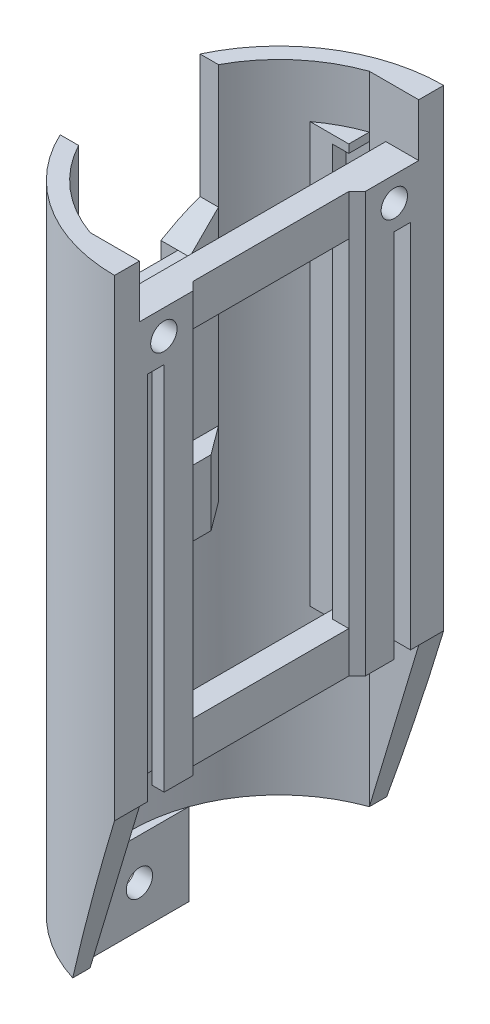
SolidWorks part; units mm, degrees
ref_plane "前视基准面" through (0, 0, 0) normal (0, 0, 1) x (1, 0, 0)
ref_plane "上视基准面" through (0, 0, 0) normal (0, 1, 0) x (1, 0, 0)
ref_plane "右视基准面" through (0, 0, 0) normal (1, 0, 0) x (0, 0, -1)
other "Configuration Table"
sketch "草图1" plane through (0, 0, 0) normal (0, 1, 0) x (1, 0, 0)
  line L0 (0, -473.638) -> (0, 23208.2609) construction
  line L1 (0, 0) -> (-4, 0) construction
  line L2 (0, 20) -> (0, -20)
  line L3 (-4, -17.5499) -> (-4, 17.5499)
  arc A0 (0, 20) -> (0, -20) centre (0, 0) ccw
  arc A1 (-4, 17.5499) -> (-4, -17.5499) centre (0, 0) ccw
  point P12 (-4, 0)
  dimension "D1" = 40
  dimension "D2" = 36
  dimension "D3" = 4
extrude "凸台-拉伸1" add sketch "草图1" along normal blind 70
sketch "草图3" plane through (0, 0, 0) normal (1, 0, 0) x (0, 0, -1)
  line L0 (-20, 0) -> (20, 0) construction
  line L1 (-16, 60) -> (16, 60) construction
  line L2 (-16, 60) -> (-16, 0) construction
  line L3 (-16, 0) -> (16, 0) construction
  line L4 (16, 60) -> (16, 0) construction
  line L5 (-20, 70) -> (20, 70) construction
  circle A0 centre (-14, 58) radius 2 construction
  circle A1 centre (14, 58) radius 2 construction
  circle A2 centre (-14, 58) radius 1
  circle A3 centre (14, 58) radius 1
  point P4 (0, 60)
  dimension "D4" = 4
  dimension "D5" = 4
  dimension "D6" = 2
  dimension "D7" = 2
  dimension "D1" = 0
  dimension "D2" = 10
  dimension "D3" = 32
extrude "切除-拉伸2" cut sketch "草图3" against normal up to surface (4 mm away) from surface up to face at (-4, 35, 0) starting at face at (0, 35, 0)
sketch "草图5" plane through (0, 0, 0) normal (0, 1, 0) x (1, 0, 0)
  line L0 (0, -1000) -> (0, 49000) construction
  line L1 (-1000, 0) -> (49000, 0) construction
  line L2 (-6, 16.9706) -> (6, 16.9706) construction
  line L3 (-6, -16.9706) -> (6, -16.9706) construction
  line L4 (0, 16.9706) -> (0, -16.9706)
  line L5 (0, -16.9706) -> (-4, -16.9706)
  line L6 (-4, -17.5499) -> (-4, 17.5499) construction
  line L7 (-4, -16.9706) -> (-4, 16.9706)
  line L8 (-4, 16.9706) -> (0, 16.9706)
  circle A0 centre (0, 0) radius 18 construction
  point P11 (0, 16.9706)
  dimension "D1" = 12
extrude "切除-拉伸4" cut sketch "草图5" against normal blind 9 from surface starting at face at (-10, 70, 0)
sketch "草图6" plane through (0, 0, 0) normal (0, 1, 0) x (1, 0, 0)
  line L0 (-4, 16.9706) -> (-6, 16.9706)
  line L1 (0, 16.9706) -> (0, 18)
  line L2 (-4, -16.9706) -> (-6, -16.9706)
  line L3 (0, -16.9706) -> (0, -18)
  line L4 (-4, 16.9706) -> (-4, -16.9706)
  line L5 (0, 16.9706) -> (-4, 16.9706)
  line L6 (0, -16.9706) -> (0, 16.9706)
  line L7 (-4, -16.9706) -> (0, -16.9706)
  line L9 (0, 16.9706) -> (-4, 16.9706)
  line L11 (-4, -16.9706) -> (0, -16.9706)
  arc A0 (0, 18) -> (-6, 16.9706) centre (0, 0) ccw
  arc A1 (-6, -16.9706) -> (0, -18) centre (0, 0) ccw
  dimension "D1" = 0
extrude "凸台-拉伸2" add sketch "草图6" against normal up to surface from surface up to face at (-10, 0, 0) starting at face at (-6.25, 70, 0)
sketch "草图7" plane through (0, 0, 0) normal (0, 1, 0) x (1, 0, 0)
  line L4 (-4, 16.9706) -> (-4, -16.9706)
  line L5 (0, 16.9706) -> (-4, 16.9706)
  line L6 (0, -16.9706) -> (0, 16.9706)
  line L7 (-4, -16.9706) -> (0, -16.9706)
  line L8 (-4, 16.9706) -> (-4, -16.9706)
  line L9 (0, 16.9706) -> (-4, 16.9706)
  line L10 (0, -16.9706) -> (0, 16.9706)
  line L11 (-4, -16.9706) -> (0, -16.9706)
  dimension "D1" = 0
extrude "切除-拉伸5" cut sketch "草图7" along normal blind 10
sketch "草图8" plane through (0, 0, 0) normal (0, 1, 0) x (1, 0, 0)
  line L0 (0, 16.9706) -> (0, -16.9706) construction
  line L1 (-6, 16.9706) -> (0, 16.9706)
  line L2 (-6, 16.9706) -> (-6, 14.4706)
  line L3 (-6, 14.4706) -> (0, 14.4706)
  line L4 (0, 16.9706) -> (0, 14.4706)
  line L6 (0, -16.9706) -> (-6, -16.9706)
  line L7 (0, -16.9706) -> (0, -14.4706)
  line L8 (0, -14.4706) -> (-6, -14.4706)
  line L9 (-6, -16.9706) -> (-6, -14.4706)
  dimension "D1" = 2.5
  dimension "D2" = 2.5
extrude "凸台-拉伸3" add sketch "草图8" against normal blind 1 from surface starting at face at (-2, 61, 0)
sketch "草图10" plane through (0, 0, 0) normal (0, 1, 0) x (1, 0, 0)
  line L0 (-6, 16.9706) -> (-6, 14.4706)
  line L1 (-6, 14.4706) -> (-10.7053, 14.4706)
  line L2 (-6, -14.4706) -> (-10.7053, -14.4706)
  line L3 (-6, -14.4706) -> (-6, -16.9706)
  arc A0 (-6, 16.9706) -> (-10.7053, 14.4706) centre (0, 0) ccw
  arc A1 (-10.7053, -14.4706) -> (-6, -16.9706) centre (0, 0) ccw
extrude "凸台-拉伸4" add sketch "草图10" along normal up to surface (70 mm away) from surface up to face at (-7.3333, 70, 0) starting at face at (-7.3333, 0, 0)
sketch "草图11" plane through (0, 0, 0) normal (0, 1, 0) x (1, 0, 0)
  line L0 (0, 16.9706) -> (0, -16.9706) construction
  line L1 (-6, 16.9706) -> (0, 16.9706)
  line L2 (-6, 16.9706) -> (-6, 14.4706)
  line L3 (-6, 14.4706) -> (0, 14.4706)
  line L4 (0, 16.9706) -> (0, 14.4706)
  line L5 (-6, 14.4706) -> (-10.7053, 14.4706) construction
  line L7 (-6, -14.4706) -> (0, -14.4706)
  line L8 (-6, -14.4706) -> (-6, -16.9706)
  line L9 (-6, -16.9706) -> (0, -16.9706)
  line L10 (0, -14.4706) -> (0, -16.9706)
  dimension "D1" = 0
extrude "凸台-拉伸5" add sketch "草图11" along normal up to surface (70 mm away) from surface up to face at (-7.2705, 70, 0) starting at face at (-4, 61, 0)
sketch "草图12" plane through (0, 0, 0) normal (0, 0, 1) x (1, 0, 0)
  line L1 (-6, 60) -> (-4, 60)
  line L2 (-6, 60) -> (-6, 61)
  line L3 (-6, 61) -> (-4, 61)
  line L4 (-4, 60) -> (-4, 61)
extrude "切除-拉伸6" cut sketch "草图12" against normal up to surface (16.9706 mm away) from surface up to face at (-3.3333, 23.3333, -16.9706) starting at face at (-3.3333, 23.3333, 16.9706)
sketch "草图14" plane through (0, 0, 0) normal (0, 1, 0) x (1, 0, 0)
  line L0 (-4, -14.4706) -> (-4, 14.4706) construction
  line L1 (-4, 10.4706) -> (-3, 10.4706)
  line L2 (-4, 10.4706) -> (-4, -10.4706)
  line L3 (-4, -10.4706) -> (-3, -10.4706)
  line L4 (-3, 10.4706) -> (-3, -10.4706)
  line L5 (-10.7053, -14.4706) -> (0, -14.4706) construction
  line L6 (-4, 14.4706) -> (0, 14.4706) construction
  line L7 (0, 14.4706) -> (0, -14.4706) construction
  line L8 (-1, 10.4706) -> (0, 10.4706)
  line L9 (-1, 10.4706) -> (-1, -10.4706)
  line L10 (-1, -10.4706) -> (0, -10.4706)
  line L11 (0, 10.4706) -> (0, -10.4706)
  line L12 (0, -14.4706) -> (-4, -14.4706) construction
  line L13 (0, 14.4706) -> (-10.7053, 14.4706) construction
  dimension "D1" = 1
  dimension "D2" = 4
  dimension "D3" = 4
  dimension "D4" = 1
  dimension "D5" = 4
  dimension "D6" = 4
extrude "切除-拉伸8" cut sketch "草图14" along normal up to surface (61 mm away) from surface up to face at (-2, 61, 0) starting at face at (-2, 10, 0)
sketch "草图15" plane through (0, 0, 0) normal (1, 0, 0) x (0, 0, -1)
  line L0 (10.4706, 61) -> (10.4706, 10) construction
  line L5 (-10.4706, 61) -> (-10.4706, 10) construction
  line L6 (10.4706, 61) -> (-10.4706, 61) construction
  line L7 (-10.4706, 10) -> (10.4706, 10) construction
  line L9 (-9.4706, 56) -> (9.4706, 56)
  line L10 (-9.4706, 56) -> (-9.4706, 15)
  line L11 (-9.4706, 15) -> (9.4706, 15)
  line L12 (9.4706, 56) -> (9.4706, 15)
  dimension "D1" = 1
  dimension "D2" = 1
  dimension "D3" = 5
  dimension "D4" = 5
extrude "切除-拉伸9" cut sketch "草图15" against normal up to surface (3 mm away) from surface up to face at (-3, 35.5, 0) starting at face at (-1, 35.5, 0)
sketch "草图17" plane through (0, 0, 0) normal (1, 0, 0) x (0, 0, -1)
  circle A0 centre (-14, 58) radius 1.6
  circle A1 centre (14, 58) radius 1.6
  dimension "D1" = 3.2
  dimension "D2" = 3.2
extrude "切除-拉伸10" cut sketch "草图17" against normal blind 2.5
sketch "草图20" plane through (0, 0, 0) normal (0, 1, 0) x (1, 0, 0)
  line L0 (-1, 10.4706) -> (0, 10.4706)
  line L1 (0, 14.4706) -> (0, 10.4706) construction
  line L2 (0, 10.4706) -> (-1, 10.4706) construction
  line L3 (0, 10.4706) -> (-1, 9.4706)
  line L4 (-1, 10.4706) -> (-1, -10.4706) construction
  line L5 (-1, 9.4706) -> (-1, 10.4706)
  line L6 (-4, 10.4706) -> (-3, 10.4706)
  line L7 (-3, 10.4706) -> (-3, 9.4706)
  line L8 (-3, -10.4706) -> (-3, 10.4706) construction
  line L9 (-3, 9.4706) -> (-4, 10.4706)
  line L10 (-4, -10.4706) -> (-3, -10.4706)
  line L11 (-3, -10.4706) -> (-3, -9.4706)
  line L12 (-3, -9.4706) -> (-4, -10.4706)
  line L13 (0, -10.4706) -> (-1, -10.4706)
  line L14 (-1, -10.4706) -> (0, -10.4706) construction
  line L15 (-1, -10.4706) -> (-1, -9.4706)
  line L16 (-1, -9.4706) -> (0, -10.4706)
  dimension "D1" = 1
  dimension "D2" = 1
  dimension "D3" = 1
  dimension "D4" = 1
  dimension "D5" = 1
extrude "凸台-拉伸11" add sketch "草图20" against normal up to surface (-10 mm away) from surface up to face at (-2, 10, 0) starting at face at (-2, 61, 0)
sketch "草图21" plane through (0, 0, 0) normal (0, 1, 0) x (1, 0, 0)
  line L0 (-4, 10.4706) -> (-4, -10.4706)
  line L1 (-4, -10.4706) -> (-3, -9.4706)
  line L2 (-3, -9.4706) -> (-3, 9.4706)
  line L3 (-3, 9.4706) -> (-4, 10.4706)
extrude "凸台-拉伸12" add sketch "草图21" against normal up to surface (-56 mm away) from surface up to face at (-2, 56, 0) starting at face at (-2, 61, 0)
sketch "草图22" plane through (0, 0, 0) normal (0, 1, 0) x (1, 0, 0)
  line L4 (-4, 10.4706) -> (-4, -10.4706)
  line L5 (-4, -10.4706) -> (-3, -9.4706)
  line L6 (-3, -9.4706) -> (-3, 9.4706)
  line L7 (-3, 9.4706) -> (-4, 10.4706)
  line L8 (-4, 10.4706) -> (-4, -10.4706)
  line L9 (-4, -10.4706) -> (-3, -9.4706)
  line L10 (-3, -9.4706) -> (-3, 9.4706)
  line L11 (-3, 9.4706) -> (-4, 10.4706)
  dimension "D1" = 0
extrude "凸台-拉伸13" add sketch "草图22" along normal up to surface (15 mm away) from surface up to face at (-2, 15, 0) starting at face at (-2, 10, 0)
sketch "草图23" plane through (0, 0, 0) normal (0, 0, 1) x (1, 0, 0)
  line L0 (-3, 56) -> (-1, 56) construction
  line L1 (-6, 61) -> (-8, 61)
  line L2 (-6, 61) -> (-6, 55)
  line L3 (-6, 55) -> (-8, 55)
  line L4 (-8, 61) -> (-8, 55)
  dimension "D1" = 1
  dimension "D2" = 2
extrude "切除-拉伸11" cut sketch "草图23" along normal up to surface (1.654 mm away) from surface up to face at (-14.3526, 35, 0) starting at face at (-5.3444, 46.1429, 14.4706)
sketch "草图24" plane through (0, 0, 0) normal (0, 0, 1) x (1, 0, 0)
  line L4 (-6, 61) -> (-8, 61)
  line L5 (-8, 61) -> (-8, 55)
  line L6 (-8, 55) -> (-6, 55)
  line L7 (-6, 55) -> (-6, 61)
  line L8 (-6, 61) -> (-8, 61)
  line L9 (-8, 61) -> (-8, 55)
  line L10 (-8, 55) -> (-6, 55)
  line L11 (-6, 55) -> (-6, 61)
  dimension "D1" = 0
extrude "切除-拉伸12" cut sketch "草图24" against normal up to surface (16.1245 mm away) up to face at (-14.3526, 35, 0)
sketch "草图25" plane through (0, 0, 0) normal (0, 1, 0) x (1, 0, 0)
  line L0 (-6, -16.9706) -> (-6, -14.4706)
  line L1 (-8, -14.4706) -> (-4, -14.4706) construction
  line L2 (-6, -14.4706) -> (-10.7053, -14.4706)
  line L3 (-10.7053, 14.4706) -> (-6, 14.4706)
  line L4 (-4, 14.4706) -> (-8, 14.4706) construction
  line L5 (-6, 14.4706) -> (-6, 16.9706)
  arc A0 (-10.7053, -14.4706) -> (-6, -16.9706) centre (0, 0) ccw
  arc A1 (-6, 16.9706) -> (-10.7053, 14.4706) centre (0, 0) ccw
extrude "切除-拉伸13" cut sketch "草图25" along normal up to surface (10 mm away) from surface up to face at (-1.25, 10, 0) starting at face at (-7.2705, 0, 0)
sketch "草图29" plane through (0, 0, 0) normal (0, 1, 0) x (1, 0, 0)
  line L0 (0, -16.9706) -> (0, -14.4706)
  line L1 (0, -14.4706) -> (-10.7053, -14.4706)
  line L2 (0, -16.9706) -> (-6, -16.9706)
  line L3 (-4, -16.9706) -> (-6, -16.9706)
  line L4 (0, -18) -> (0, -16.9706)
  line L5 (0, -16.9706) -> (-4, -16.9706)
  line L6 (-4, -16.9706) -> (-6, -16.9706) construction
  line L8 (0, -16.9706) -> (-4, -16.9706) construction
  line L9 (-6, 16.9706) -> (-4, 16.9706)
  line L10 (0, 16.9706) -> (0, 18)
  line L11 (-4, 16.9706) -> (0, 16.9706)
  line L12 (-6, 16.9706) -> (-4, 16.9706) construction
  line L14 (-4, 16.9706) -> (0, 16.9706) construction
  line L15 (-6, 16.9706) -> (0, 16.9706)
  line L16 (0, 16.9706) -> (0, 14.4706)
  line L17 (0, 14.4706) -> (-10.7053, 14.4706)
  arc A0 (-10.7053, -14.4706) -> (-6, -16.9706) centre (0, 0) ccw
  arc A1 (-6, -16.9706) -> (0, -18) centre (0, 0) ccw
  arc A3 (0, 18) -> (-6, 16.9706) centre (0, 0) ccw
  arc A5 (-6, 16.9706) -> (-10.7053, 14.4706) centre (0, 0) ccw
  dimension "D1" = 0
  dimension "D2" = 0
extrude "切除-拉伸18" cut sketch "草图29" against normal up to surface (-61 mm away) from surface up to face at (-1.25, 61, 0) starting at face at (-8.1175, 70, 0)
sketch "草图30" plane through (0, 0, 0) normal (0, 1, 0) x (1, 0, 0)
  line L0 (-8, 16.1245) -> (-8, 14.4706)
  line L1 (-8, 14.4706) -> (-4, 14.4706)
  line L2 (-4, -16.9706) -> (-4, 16.9706) construction
  line L3 (-4, 14.4706) -> (-4, 16.9706)
  line L4 (-6, 16.9706) -> (0, 16.9706) construction
  line L5 (-4, 16.9706) -> (-6, 16.9706)
  line L6 (-8, -16.1245) -> (-8, -14.4706)
  line L7 (-8, -14.4706) -> (-4, -14.4706)
  line L8 (-4, -14.4706) -> (-4, -16.9706)
  line L9 (-4, -16.9706) -> (-6, -16.9706)
  arc A0 (-6, 16.9706) -> (-8, 16.1245) centre (0, 0) ccw
  arc A1 (-8, -16.1245) -> (-6, -16.9706) centre (0, 0) ccw
extrude "凸台-拉伸16" add sketch "草图30" against normal blind 1 from surface starting at face at (-8.9139, 61, -15.0418)
sketch "草图31" plane through (0, 0, 0) normal (0, 1, 0) x (1, 0, 0)
  line L4 (0, -20) -> (0, -16.9706)
  line L5 (0, -16.9706) -> (-6, -16.9706)
  line L6 (-6, 16.9706) -> (0, 16.9706)
  line L7 (0, 16.9706) -> (0, 20)
  line L8 (0, -20) -> (0, -16.9706)
  line L9 (0, -16.9706) -> (-6, -16.9706)
  line L10 (-6, 16.9706) -> (0, 16.9706)
  line L11 (0, 16.9706) -> (0, 20)
  arc A2 (-6, 16.9706) -> (-6, -16.9706) centre (0, 0) ccw
  arc A3 (0, 20) -> (0, -20) centre (0, 0) ccw
  arc A4 (-6, 16.9706) -> (-6, -16.9706) centre (0, 0) ccw
  arc A5 (0, 20) -> (0, -20) centre (0, 0) ccw
  dimension "D1" = 0
extrude "凸台-拉伸17" add sketch "草图31" along normal blind 2.4 from surface starting at face at (-7.3333, 70, 0)
sketch "草图32" plane through (0, 0, 0) normal (0, 1, 0) x (1, 0, 0)
  line L4 (0, 16.9706) -> (0, 20)
  line L5 (0, -20) -> (0, -16.9706)
  line L6 (0, -16.9706) -> (-6, -16.9706)
  line L7 (-6, 16.9706) -> (0, 16.9706)
  line L8 (0, 16.9706) -> (0, 20)
  line L9 (0, -20) -> (0, -16.9706)
  line L10 (0, -16.9706) -> (-6, -16.9706)
  line L11 (-6, 16.9706) -> (0, 16.9706)
  arc A2 (0, 20) -> (0, -20) centre (0, 0) ccw
  arc A3 (-6, 16.9706) -> (-6, -16.9706) centre (0, 0) ccw
  arc A4 (0, 20) -> (0, -20) centre (0, 0) ccw
  arc A5 (-6, 16.9706) -> (-6, -16.9706) centre (0, 0) ccw
  dimension "D1" = 0
extrude "切除-拉伸19" cut sketch "草图32" against normal blind 5 from surface starting at face at (-7.3333, 72.4, 0)
sketch "草图33" plane through (0, 0, 0) normal (0, 1, 0) x (1, 0, 0)
  line L0 (-1000, 0) -> (49000, 0) construction
  line L1 (-17.2916, -5) -> (-17.2916, 5)
  line L2 (-17.2916, 5) -> (-19.3649, 5)
  line L3 (-17.2916, -5) -> (-19.3649, -5)
  arc A0 (-17.2916, 5) -> (-17.2916, -5) centre (0, 0) ccw construction
  arc A1 (-19.3649, 5) -> (-19.3649, -5) centre (0, 0) ccw
  point P11 (-17.2916, 0)
  dimension "D1" = 10
extrude "切除-拉伸20" cut sketch "草图33" against normal blind 45 from surface starting at face at (-7.3333, 67.4, 0)
sketch "草图39" plane through (0, 0, 0) normal (0, 1, 0) x (1, 0, 0)
  line L0 (-20, 0) -> (-15.8666, 0) construction
  line L1 (-15.8666, -8.5) -> (-15.8666, 8.5)
  line L2 (-15.8666, 8.5) -> (-18.1039, 8.5)
  line L3 (-15.8666, -8.5) -> (-18.1039, -8.5)
  arc A0 (-18.1039, 8.5) -> (-18.1039, -8.5) centre (0, 0) ccw
  arc A1 (-15.8666, 8.5) -> (-15.8666, -8.5) centre (0, 0) ccw construction
  point P11 (-15.8666, 0)
  dimension "D1" = 17
extrude "切除-拉伸22" cut sketch "草图39" against normal blind 15 from surface contours L2 A0 L3 L1 region at (-17.6683, 0, 0) starting at face at (-9.3339, 67.4, 13.7237)
sketch "草图40" plane through (0, 0, 0) normal (1, 0, 0) x (0, 0, -1)
  line L0 (-5, 52.4) -> (-8.5, 52.4)
  line L1 (-8.5, 52.4) -> (-5, 48.9)
  line L2 (-5, 22.4) -> (-5, 52.4) construction
  line L3 (-5, 48.9) -> (-5, 52.4)
  line L4 (8.5, 52.4) -> (5, 52.4)
  line L5 (5, 52.4) -> (5, 48.9)
  line L6 (5, 22.4) -> (5, 52.4) construction
  line L7 (5, 48.9) -> (8.5, 52.4)
  dimension "D1" = 3.5
  dimension "D2" = 3.5
extrude "切除-拉伸25" cut sketch "草图40" against normal through all
sketch "草图41" plane through (0, 0, 0) normal (0, 1, 0) x (1, 0, 0)
  line L0 (-1000, 0) -> (49000, 0) construction
  line L1 (-15.8666, 8.5) -> (-15.8666, -8.5)
  line L2 (-17.2916, 5) -> (-17.2916, -5)
  arc A0 (-17.2916, -5) -> (-15.8666, -8.5) centre (0, 0) ccw
  arc A1 (-15.8666, 8.5) -> (-17.2916, 5) centre (0, 0) ccw
extrude "凸台-拉伸24" add sketch "草图41" along normal up to vertex (48.9 mm away) from surface up to point (-17.2916, 48.9, -5) starting at face at (-18.6641, 22.4, 0)
sketch "草图42" plane through (0, 0, 0) normal (1, 0, 0) x (0, 0, -1)
  line L0 (-8.5, 52.4) -> (-8.5, 48.9)
  line L1 (-8.5, 48.9) -> (-5, 48.9)
  line L2 (-5, 48.9) -> (-8.5, 52.4)
  line L3 (8.5, 52.4) -> (8.5, 48.9)
  line L4 (8.5, 48.9) -> (5, 48.9)
  line L5 (5, 48.9) -> (8.5, 52.4)
extrude "凸台-拉伸25" add sketch "草图42" against normal up to surface (2.2372 mm away) from surface up to face at (-14.5014, 43.0882, 0) starting at face at (-15.8666, 35.65, 0)
sketch "草图43" plane through (0, 0, 0) normal (0, 1, 0) x (1, 0, 0)
  line L0 (-15.8666, 8.5) -> (-15.8666, -8.5)
  arc A0 (-15.8666, 8.5) -> (-15.8666, -8.5) centre (0, 0) ccw
extrude "凸台-拉伸26" add sketch "草图43" against normal blind 1 from surface starting at face at (-16.6252, 22.4, 0)
sketch "草图44" plane through (0, 0, 0) normal (0, 1, 0) x (1, 0, 0)
  line L0 (-1000, 0) -> (49000, 0) construction
  line L1 (-15.8666, 0) -> (-13.2666, 0) construction
  line L2 (-15.8666, 5) -> (-15.8666, -5) construction
  line L3 (-13.2666, -5) -> (-13.2666, 5)
  line L4 (-13.2666, 5) -> (-15.8666, 8.5)
  line L5 (-13.2666, -5) -> (-15.8666, -8.5)
  line L6 (-15.8666, 8.5) -> (-15.8666, -8.5)
  circle A1 centre (0, 0) radius 18 construction
  point P12 (-13.2666, 0)
  dimension "D1" = 2.6
  dimension "D2" = 10
extrude "凸台-拉伸27" add sketch "草图44" along normal blind 8 from surface starting at face at (-16.9333, 21.4, 0)
sketch "草图45" plane through (0, 0, 0) normal (1, 0, 0) x (0, 0, -1)
  line L0 (0, 67.4) -> (0, 21.4) construction
  line L2 (5, 22.4) -> (-5, 22.4) construction
  circle A0 centre (0, 26.4) radius 1
  dimension "D1" = 2
  dimension "D2" = 4
extrude "切除-拉伸26" cut sketch "草图45" along normal up to surface (-13.2666 mm away) from surface up to face at (-13.2666, 25.4, 0) starting at face at (-17.2916, 35.65, 0)
sketch "草图46" plane through (0, 0, 0) normal (0, 1, 0) x (1, 0, 0)
  line L0 (-15.8666, 5) -> (-15.8666, -5) construction
  line L1 (-15.8666, 2) -> (-14.2666, 2)
  line L2 (-15.8666, 2) -> (-15.8666, -2)
  line L3 (-15.8666, -2) -> (-14.2666, -2)
  line L4 (-14.2666, 2) -> (-14.2666, -2)
  line L5 (-17.2916, -5) -> (-17.2916, 5) construction
  point P8 (-17.2916, 0)
  point P9 (-15.8666, 0)
  dimension "D1" = 4
  dimension "D2" = 1.6
extrude "切除-拉伸27" cut sketch "草图46" along normal blind 5 from surface starting at face at (-15.1, 21.4, 0)
sketch "草图47" plane through (0, 0, 0) normal (1, 0, 0) x (0, 0, -1)
  line L1 (0, 24.0906) -> (2, 25.2453)
  line L2 (2, 25.2453) -> (2, 27.5547)
  line L3 (2, 27.5547) -> (0, 28.7094)
  line L4 (0, 28.7094) -> (-2, 27.5547)
  line L5 (-2, 27.5547) -> (-2, 25.2453)
  line L6 (-2, 25.2453) -> (0, 24.0906)
  circle A0 centre (0, 26.4) radius 2 construction
  dimension "D1" = 4
extrude "切除-拉伸28" cut sketch "草图47" against normal up to surface (15.8666 mm away) from surface up to face at (-15.8666, 24.5667, 0) starting at face at (-14.2666, 24.5667, 0)
sketch "草图48" plane through (0, 0, 0) normal (1, 0, 0) x (0, 0, -1)
  line L0 (5, 22.4) -> (3, 22.4)
  line L1 (5, 22.4) -> (-5, 22.4) construction
  line L2 (3, 22.4) -> (5, 24.4)
  line L3 (5, 22.4) -> (5, 48.9) construction
  line L4 (5, 24.4) -> (5, 22.4)
  line L5 (-5, 22.4) -> (-5, 24.4)
  line L6 (-5, 22.4) -> (-5, 48.9) construction
  line L7 (-5, 24.4) -> (-3, 22.4)
  line L8 (-3, 22.4) -> (-5, 22.4)
  dimension "D1" = 2
  dimension "D2" = 2
  dimension "D3" = 2
  dimension "D4" = 2
extrude "凸台-拉伸28" add sketch "草图48" against normal up to surface (2.0733 mm away) from surface up to face at (-14.5014, 43.0882, 0) starting at face at (-17.2916, 26.4, 1)
sketch "草图49" plane through (0, 0, 0) normal (0, 1, 0) x (1, 0, 0)
  line L1 (-6, -16.9706) -> (-4, -16.9706)
  line L2 (-6, -16.9706) -> (-6, 16.9706)
  line L3 (-6, 16.9706) -> (-4, 16.9706)
  line L4 (-4, -16.9706) -> (-4, 16.9706)
extrude "切除-拉伸29" cut sketch "草图49" along normal through all
sketch "草图50" plane through (0, 0, 0) normal (0, 1, 0) x (1, 0, 0)
  line L0 (0, 16.9706) -> (0, 15.9706) construction
  line L1 (0, 16.9706) -> (0, 10.4706) construction
  line L2 (0, 15.9706) -> (-3, 15.9706)
  line L3 (-3, 15.9706) -> (-3, 11.9706)
  line L4 (-3, 11.9706) -> (-1.5, 11.9706)
  line L5 (-1.5, 11.9706) -> (-1.5, 13.9706)
  line L6 (-1.5, 13.9706) -> (0, 13.9706)
  line L7 (-1000, 0) -> (49000, 0) construction
  line L8 (-1.5, -13.9706) -> (0, -13.9706)
  line L9 (-1.5, -11.9706) -> (-1.5, -13.9706)
  line L10 (-3, -11.9706) -> (-1.5, -11.9706)
  line L11 (-3, -15.9706) -> (-3, -11.9706)
  line L12 (0, -15.9706) -> (-3, -15.9706)
  line L13 (0, -16.9706) -> (0, -15.9706) construction
  line L14 (0, 15.9706) -> (0, 13.9706)
  line L15 (0, -13.9706) -> (0, -15.9706)
  dimension "D1" = 1
  dimension "D2" = 3
  dimension "D3" = 1.5
  dimension "D4" = 2
  dimension "D5" = 2
extrude "切除-拉伸30" cut sketch "草图50" along normal blind 45 from surface starting at face at (-1.25, 10, 0)
sketch "草图51" plane through (0, 0, 0) normal (0, 1, 0) x (1, 0, 0)
  line L0 (0, -11.9706) -> (3, -11.9706)
  line L1 (0, -13.9706) -> (0, -10.4706) construction
  line L2 (3, -11.9706) -> (3, -14.9706)
  line L3 (3, -14.9706) -> (0, -14.9706) construction
  line L4 (1.5, -14.9706) -> (1.5, -13.9706)
  line L5 (1.5, -13.9706) -> (0, -13.9706)
  line L6 (-3, -11.9706) -> (-1.5, -11.9706) construction
  line L7 (1.5, -14.9706) -> (3, -14.9706)
  line L8 (0, -13.9706) -> (0, -11.9706)
  line L9 (-1000, 0) -> (49000, 0) construction
  line L10 (3, 14.9706) -> (0, 14.9706) construction
  line L11 (0, 13.9706) -> (0, 11.9706)
  line L12 (1.5, 14.9706) -> (3, 14.9706)
  line L13 (1.5, 13.9706) -> (0, 13.9706)
  line L14 (1.5, 14.9706) -> (1.5, 13.9706)
  line L15 (3, 11.9706) -> (3, 14.9706)
  line L16 (0, 11.9706) -> (3, 11.9706)
  dimension "D1" = 3
  dimension "D2" = 3
  dimension "D3" = 3
extrude "凸台-拉伸29" add sketch "草图51" along normal blind 45 from surface starting at face at (-1.4, 10, 0)
sketch "草图52" plane through (0, 0, 0) normal (0, 1, 0) x (1, 0, 0)
  line L4 (0, -16.9706) -> (-6, -16.9706)
  line L5 (0, -20) -> (0, -16.9706)
  line L6 (0, 16.9706) -> (0, 20)
  line L7 (-6, 16.9706) -> (0, 16.9706)
  line L8 (0, -16.9706) -> (-6, -16.9706)
  line L9 (0, -20) -> (0, -16.9706)
  line L10 (0, 16.9706) -> (0, 20)
  line L11 (-6, 16.9706) -> (0, 16.9706)
  arc A2 (-6, 16.9706) -> (-6, -16.9706) centre (0, 0) ccw
  arc A3 (0, 20) -> (0, -20) centre (0, 0) ccw
  arc A4 (-6, 16.9706) -> (-6, -16.9706) centre (0, 0) ccw
  arc A5 (0, 20) -> (0, -20) centre (0, 0) ccw
  dimension "D1" = 0
extrude "凸台-拉伸30" add sketch "草图52" against normal blind 10
sketch "草图58" plane through (0, 0, 0) normal (0, 1, 0) x (1, 0, 0)
  line L0 (1.5, -13.9706) -> (1.5, -14.9706) construction
  line L1 (1.5, -14.9706) -> (3, -14.9706) construction
  line L2 (3, -14.9706) -> (3, -11.9706) construction
  line L3 (3, -11.9706) -> (0, -11.9706) construction
  line L4 (0, -11.9706) -> (0, -13.9706) construction
  line L5 (0, -13.9706) -> (1.5, -13.9706) construction
  line L6 (1.5, 13.9706) -> (0, 13.9706) construction
  line L7 (0, 13.9706) -> (0, 11.9706) construction
  line L8 (0, 11.9706) -> (3, 11.9706) construction
  line L9 (3, 11.9706) -> (3, 14.9706) construction
  line L10 (3, 14.9706) -> (1.5, 14.9706) construction
  line L11 (1.5, 14.9706) -> (1.5, 13.9706) construction
  line L12 (1.5, -13.9706) -> (1.5, -14.9706)
  line L13 (1.5, -14.9706) -> (3, -14.9706)
  line L14 (3, -14.9706) -> (3, -11.9706)
  line L15 (3, -11.9706) -> (0, -11.9706)
  line L16 (0, -11.9706) -> (0, -13.9706)
  line L17 (0, -13.9706) -> (1.5, -13.9706)
  line L18 (1.5, 13.9706) -> (0, 13.9706)
  line L19 (0, 13.9706) -> (0, 11.9706)
  line L20 (0, 11.9706) -> (3, 11.9706)
  line L21 (3, 11.9706) -> (3, 14.9706)
  line L22 (3, 14.9706) -> (1.5, 14.9706)
  line L23 (1.5, 14.9706) -> (1.5, 13.9706)
extrude "切除-拉伸34" cut sketch "草图58" along normal up to surface (55 mm away) from surface up to face at (1.5, 55, 13.6372) starting at face at (-0.3571, 10, 0)
sketch "草图60" plane through (0, 0, 0) normal (0, 0, 1) x (1, 0, 0)
  line L0 (0, 10) -> (-6, -10)
  line L1 (-6, -10) -> (0, -10)
  line L2 (0, -10) -> (0, 10)
extrude "切除-拉伸35" cut sketch "草图60" against normal through all and the other way through all
sketch "草图61" plane through (0, 0, 0) normal (0, 1, 0) x (1, 0, 0)
  line L0 (-1000, 0) -> (49000, 0) construction
  line L1 (-16.9706, 6) -> (-16.9706, -6)
  line L2 (-16.9706, -6) -> (-19.0788, -6)
  line L3 (-16.9706, 6) -> (-19.0788, 6)
  arc A0 (-19.0788, 6) -> (-19.0788, -6) centre (0, 0) ccw
  arc A1 (-16.9706, 6) -> (-16.9706, -6) centre (0, 0) ccw construction
  point P11 (-16.9706, 0)
  dimension "D1" = 12
extrude "凸台-拉伸32" add sketch "草图61" against normal blind 10 from surface starting at face at (-12.5, -10, 0)
sketch "草图62" plane through (0, 0, 0) normal (0, 1, 0) x (1, 0, 0)
  line L0 (-19.0788, -6) -> (-19.0788, 6)
  arc A0 (-19.0788, 6) -> (-19.0788, -6) centre (0, 0) ccw construction
  arc A1 (-19.0788, 6) -> (-19.0788, -6) centre (0, 0) ccw
extrude "切除-拉伸36" cut sketch "草图62" against normal blind 10 from surface starting at face at (-12.7237, -10, 12.7237)
sketch "草图63" plane through (0, 0, 0) normal (1, 0, 0) x (0, 0, -1)
  line L0 (-6, -20) -> (6, -20) construction
  line L1 (6, -20) -> (6, -10) construction
  circle A0 centre (0, -15) radius 1.6
  dimension "D1" = 3.2
  dimension "D2" = 5
  dimension "D3" = 6
extrude "切除-拉伸37" cut sketch "草图63" against normal through all
sketch "草图65" plane through (0, 0, 0) normal (1, 0, 0) x (0, 0, -1)
  line L0 (-6, -10) -> (6, -10)
  line L3 (6, -10) -> (6, -14)
  line L11 (6, -20) -> (6, -10) construction
  line L12 (6, -14) -> (3, -11)
  line L13 (3, -11) -> (-3, -11)
  line L14 (-3, -11) -> (-6, -14)
  line L15 (-6, -20) -> (-6, -10) construction
  line L16 (-6, -14) -> (-6, -10)
  dimension "D1" = 4
  dimension "D2" = 6
  dimension "D3" = 3
  dimension "D4" = 4
  dimension "D5" = 3
extrude "凸台-拉伸33" add sketch "草图65" against normal up to surface from surface up to face at (-13.7534, 30.313, 0) starting at face at (-19.0788, -15, -1.6)
